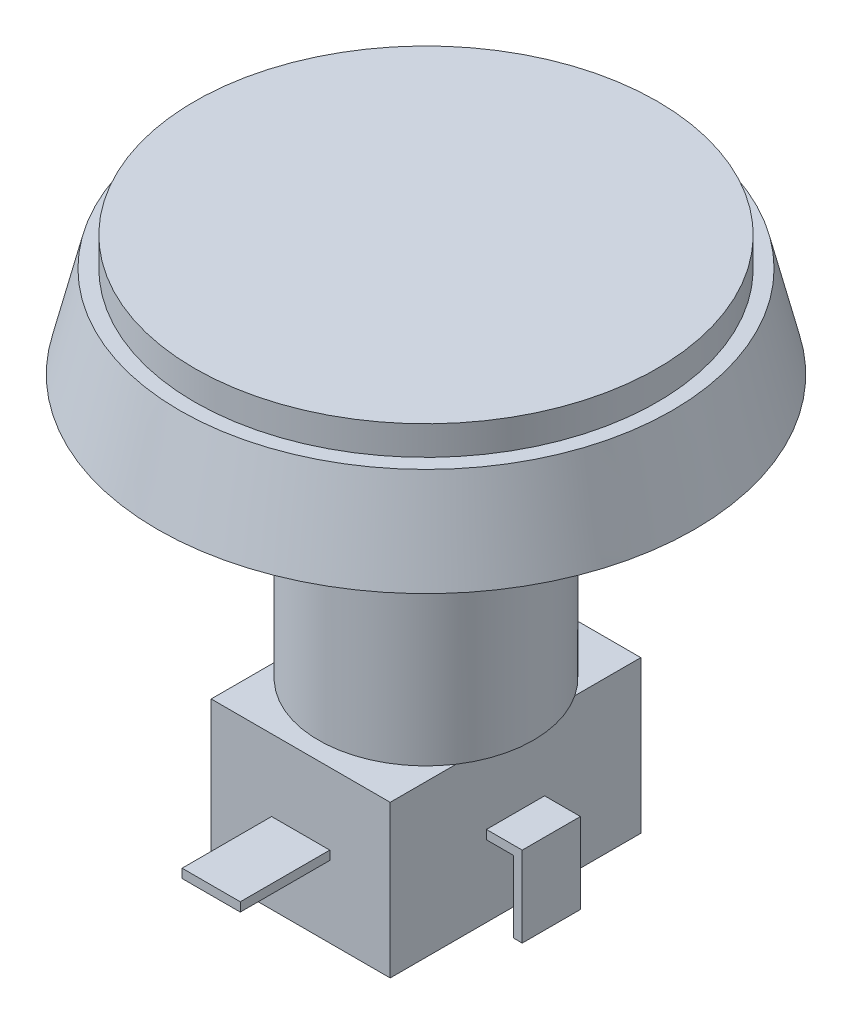
SolidWorks part; units mm, degrees
ref_plane "Front Plane" through (0, 0, 0) normal (0, 0, 1) x (1, 0, 0)
ref_plane "Top Plane" through (0, 0, 0) normal (0, 1, 0) x (1, 0, 0)
ref_plane "Right Plane" through (0, 0, 0) normal (1, 0, 0) x (0, 0, -1)
ref_plane "Loft Plane" through (0, 10.25, 0) normal (0, 1, 0) x (1, 0, 0)
sketch "Sketch1" plane through (0, 0, 0) normal (0, 1, 0) x (1, 0, 0)
  circle A0 centre (0, 0) radius 30
  dimension "D1" = 60
sketch "Sketch2" plane through (0, 10.25, 0) normal (0, 1, 0) x (1, 0, 0)
  circle A0 centre (0, 0) radius 27.5
  dimension "D1" = 55
loft "Frame" add profiles "Sketch1", "Sketch2" connector at (-29.0196, 0, 7.6067) connector at (-25.3401, 10.25, 10.6832)
sketch "Sketch3" plane through (0, 10.25, 0) normal (0, 1, 0) x (1, 0, 0)
  circle A0 centre (0, 0) radius 25.85
  dimension "D1" = 51.7
extrude "Button" add sketch "Sketch3" along normal blind 3.25
sketch "Sketch4" plane through (0, 0, 0) normal (0, -1, 0) x (1, 0, 0)
  circle A0 centre (0, 0) radius 12
  dimension "D1" = 24
extrude "Thread" add sketch "Sketch4" along normal blind 29.4
sketch "Sketch5" plane through (0, 0, 0) normal (0, -1, 0) x (1, 0, 0)
  line L0 (0, -18.75) -> (0, 18.75) construction
  circle A0 centre (0, 0) radius 18.75 construction
  circle A1 centre (0, 18.75) radius 1.675
  circle A2 centre (0, -18.75) radius 1.675
  point P6 (0, 0)
  dimension "D1" = 37.5
  dimension "D2" = 3.35
extrude "Alignment studs" add sketch "Sketch5" along normal blind 3.7
sketch "Sketch6" plane through (0, 0, 0) normal (1, 0, 0) x (0, 0, -1)
  line L0 (0, -29.4) -> (0, -46.4) construction
  line L3 (14, -29.4) -> (-14, -29.4)
  line L4 (14, -29.4) -> (14, -46.4)
  line L5 (14, -46.4) -> (-14, -46.4)
  line L6 (-14, -29.4) -> (-14, -46.4)
  line L7 (0, 23.595) -> (0, -23.595) construction
  line L8 (-12, -29.4) -> (12, -29.4) construction
  line L9 (-14, -37.4) -> (-24, -37.4)
  line L10 (-24, -37.4) -> (-24, -38.4)
  line L11 (-24, -38.4) -> (-14, -38.4)
  line L12 (-24, -37.9) -> (-14, -37.9) construction
  line L13 (0.5, -46.4) -> (0.5, -50.4)
  line L14 (0.5, -50.4) -> (-9, -50.4)
  line L15 (-9, -50.4) -> (-9, -49.4)
  line L16 (-9, -49.4) -> (-0.5, -49.4)
  line L17 (-0.5, -49.4) -> (-0.5, -46.4)
  dimension "D1" = 28
  dimension "D2" = 17
  dimension "D3" = 10
  dimension "D4" = 1
  dimension "D5" = 4
  dimension "D6" = 1
  dimension "D7" = 1
  dimension "D8" = 9.5
extrude "Boss-Extrude1" add sketch "Sketch6" along normal mid plane 20 contours L3 L6 L5 L4 region at (0, -37.9, 0)
extrude "Boss-Extrude2" add sketch "Sketch6<3>" along normal mid plane 6.5 contours L17 L16 L15 L14 L13 L5 | L10 L11 L6 L9 region at (0, -37.9, 19) region at (0, -49.42, 3.23)
sketch "Sketch6<3>" plane through (0, 0, 0) normal (1, 0, 0) x (0, 0, -1) same geometry as "Sketch6"
sketch "Sketch7" plane through (0, 0, 0) normal (0, 0, 1) x (1, 0, 0)
  line L0 (0, 68.7123) -> (0, -68.7123) construction
  line L2 (-10, -37.4) -> (-14, -37.4)
  line L3 (-10, -29.4) -> (-10, -46.4) construction
  line L4 (-14, -37.4) -> (-14, -46.4)
  line L5 (-14, -46.4) -> (-13, -46.4)
  line L6 (-13, -46.4) -> (-13, -38.4)
  line L7 (-13, -38.4) -> (-10, -38.4)
  line L8 (-12, 0) -> (-12, -29.4) construction
  line L9 (10, -46.4) -> (-10, -46.4) construction
  line L10 (-10, -37.4) -> (-10, -38.4)
  line L11 (10, -37.4) -> (10, -38.4)
  line L12 (13, -38.4) -> (10, -38.4)
  line L13 (13, -46.4) -> (13, -38.4)
  line L14 (14, -46.4) -> (13, -46.4)
  line L15 (14, -37.4) -> (14, -46.4)
  line L16 (10, -37.4) -> (14, -37.4)
  point P3 (0, 0)
  dimension "D1" = 1
  dimension "D2" = 1
  dimension "D3" = 2
  dimension "D4" = 9
extrude "Boss-Extrude3" add sketch "Sketch7" along normal mid plane 6.5
